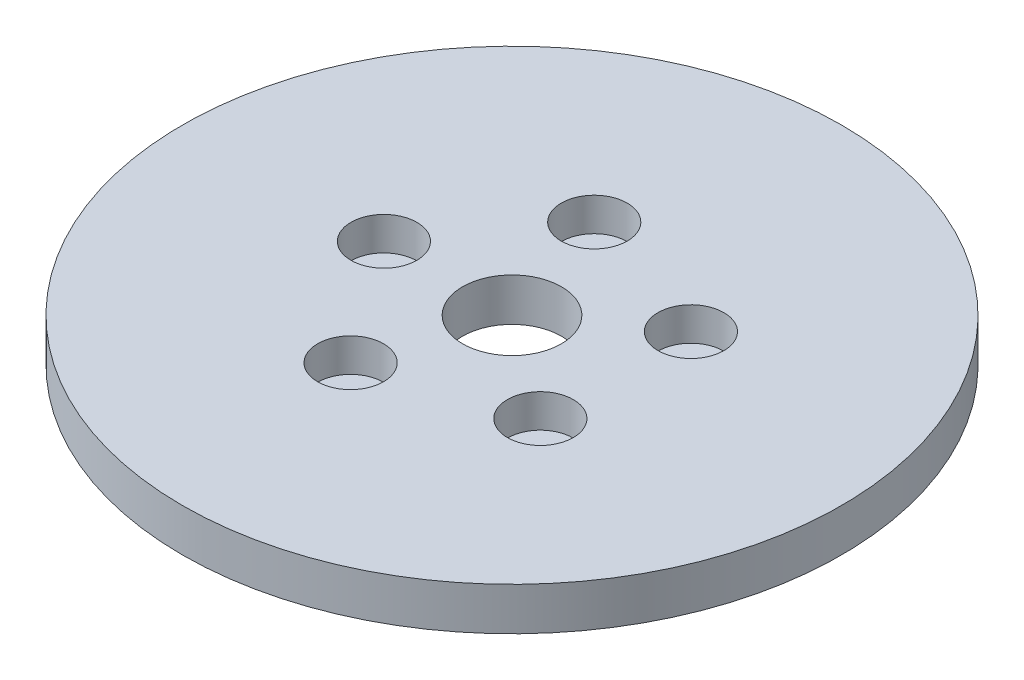
SolidWorks part; units mm, degrees
ref_plane "Front Plane" through (0, 0, 0) normal (0, 0, 1) x (1, 0, 0)
ref_plane "Top Plane" through (0, 0, 0) normal (0, 1, 0) x (1, 0, 0)
ref_plane "Right Plane" through (0, 0, 0) normal (1, 0, 0) x (0, 0, -1)
sketch "Sketch1" plane through (0, 0, 0) normal (0, 1, 0) x (1, 0, 0)
  circle A0 centre (0, 0) radius 100
  dimension "FLANGE_OD" = 200
extrude "Boss-Extrude1" add sketch "Sketch1" along normal blind 13
sketch "Sketch2" plane through (0, 0, 0) normal (0, 1, 0) x (1, 0, 0)
  circle A0 centre (0, 0) radius 15
  dimension "BORE_D" = 30
extrude "Cut-Extrude1" cut sketch "Sketch2" along normal through all
sketch "Sketch3" plane through (0, 13, 0) normal (0, 1, 0) x (1, 0, 0)
  circle A0 centre (0, 0) radius 38.8686 construction
  circle A1 centre (-38.8686, 0) radius 10
  dimension "BOLT_D" = 20
  dimension "BOLT_PCD" = 77.7372
extrude "Cut-Extrude2" cut sketch "Sketch3" against normal blind 10.1231
pattern_circular "CirPattern1" count 5 over 360 about axis through (0, 0, 0) along (0, 1, 0) of "Cut-Extrude2"
